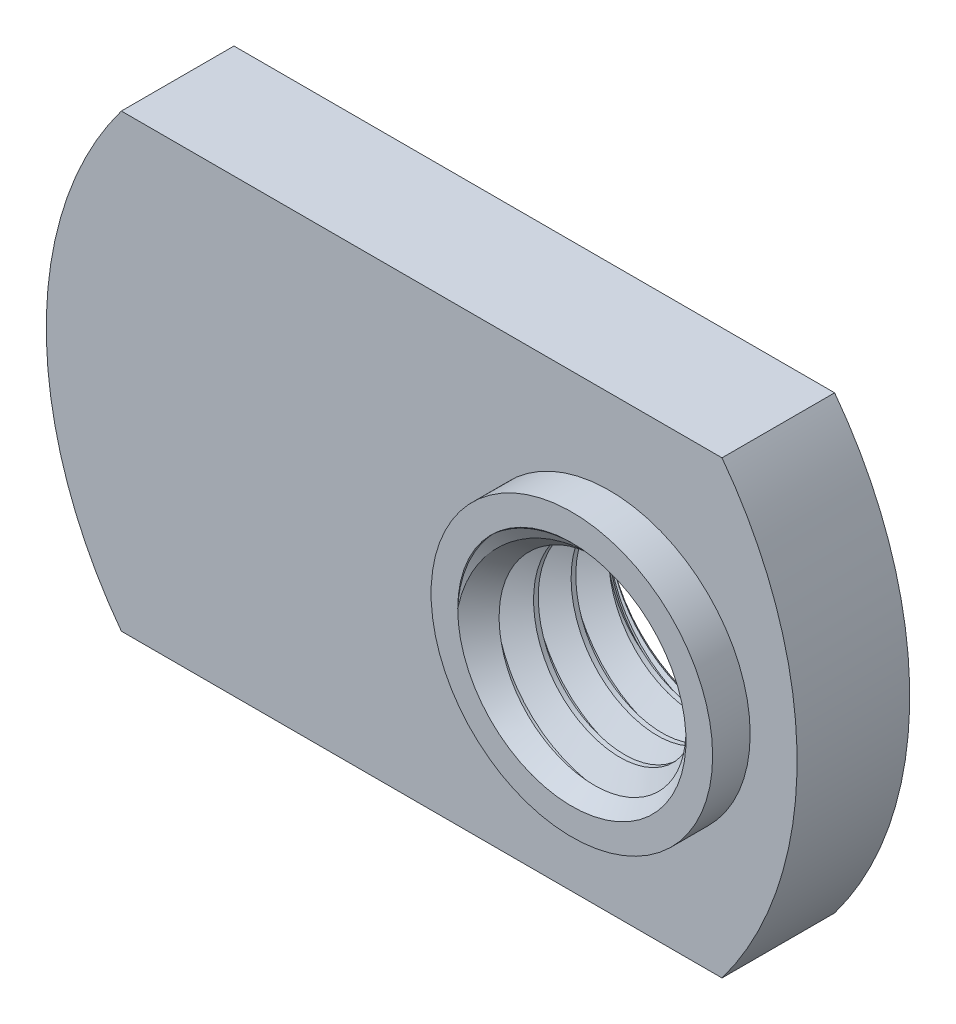
SolidWorks part; units mm, degrees
note: '?' marks a value the reader was unsure of.
ref_plane "Front Plane" through (0, 0, 0) normal (0, 0, 1) x (1, 0, 0)
ref_plane "Top Plane" through (0, 0, 0) normal (0, 1, 0) x (1, 0, 0)
ref_plane "Right Plane" through (0, 0, 0) normal (1, 0, 0) x (0, 0, -1)
sketch "Sketch1" plane through (0, 0, 0) normal (0, 0, 1) x (1, 0, 0)
  line L0 (-6.35, 4.7625) -> (6.35, 4.7625)
  line L1 (-6.35, -4.7625) -> (6.35, -4.7625)
  line L2 (0, 0) -> (3.9688, 0) construction
  line L3 (3.9688, 0) -> (7.9375, 0) construction
  arc A0 (6.35, -4.7625) -> (6.35, 4.7625) centre (0, 0) ccw
  arc A2 (-6.35, 4.7625) -> (-6.35, -4.7625) centre (0, 0) ccw
  circle A3 centre (3.9688, 0) radius 2.413
  dimension "D1" = 4.826
  dimension "width" = 9.525
extrude "Extrude1" add sketch "Sketch1" along normal blind 2.3813
sketch "Sketch2" plane through (0, 0, 2.3813) normal (0, 0, 1) x (1, 0, 0)
  circle A0 centre (3.9688, 0) radius 2.9766
  circle A1 centre (3.9688, 0) radius 2.413
  circle A2 centre (3.9688, 0) radius 2.413 construction
extrude "Extrude2" add sketch "Sketch2" along normal blind 0.7937
sketch "Sketch3" plane through (0, 0, 0) normal (0, 0, -1) x (-1, 0, 0)
  circle A1 centre (-3.9688, 0) radius 2.413
  circle A2 centre (-3.9688, 0) radius 2.413 construction
curve "Helix/Spiral1" pitch 0.7937 height 7.1437 turns 9 parameters "pitch"=0.7937
sketch "Sketch4" plane through (0, 0, 0) normal (0, 1, 0) x (1, 0, 0)
  line L0 (1.5557, 0.6945) -> (1.5557, 0)
  line L1 (1.5557, 0) -> (2.0713, 0.2977)
  line L2 (2.0713, 0.2977) -> (2.0713, 0.3969)
  line L3 (2.0713, 0.3969) -> (1.5557, 0.6945)
  line L4 (2.0713, 0.3473) -> (1.5557, 0.3473) construction
  line L5 (1.8135, 0.1488) -> (1.8135, 0.5457) construction
  dimension "D1" = 0.0992
  dimension "D2" = 0.3969
  dimension "D3" = 60
sweep "Sweep1" add profiles "Sketch4" path "Helix/Spiral1"
sketch "Sketch5" plane through (0, 0, 0) normal (0, 0, -1) x (-1, 0, 0)
  line L2 (-6.35, -4.7625) -> (6.35, -4.7625)
  line L3 (-6.35, -4.7625) -> (6.35, -4.7625)
  line L4 (6.35, 4.7625) -> (-6.35, 4.7625)
  line L5 (6.35, 4.7625) -> (-6.35, 4.7625)
  arc A1 (-6.35, 4.7625) -> (-6.35, -4.7625) centre (0, 0) ccw
  arc A2 (-6.35, 4.7625) -> (-6.35, -4.7625) centre (0, 0) ccw
  arc A4 (6.35, -4.7625) -> (6.35, 4.7625) centre (0, 0) ccw
  arc A5 (6.35, -4.7625) -> (6.35, 4.7625) centre (0, 0) ccw
  dimension "D1" = 0
extrude "Cut-Extrude1" cut sketch "Sketch5" along normal through all
sketch "Sketch6" plane through (0, 0, 0) normal (0, 0, -1) x (-1, 0, 0)
  circle A1 centre (-3.9688, 0) radius 2.413
  circle A2 centre (-3.9688, 0) radius 2.413 construction
extrude "Cut-Extrude2" cut sketch "Sketch6" against normal through all draft 45
sketch "Sketch7" plane through (0, 0, 3.175) normal (0, 0, 1) x (1, 0, 0)
  circle A1 centre (3.9688, 0) radius 2.9766
  circle A2 centre (3.9688, 0) radius 2.9766
  dimension "D1" = 0
extrude "Cut-Extrude3" cut sketch "Sketch7" along normal through all
sketch "Sketch8" plane through (0, 0, 3.175) normal (0, 0, 1) x (1, 0, 0)
  circle A1 centre (3.9688, 0) radius 2.413
  circle A2 centre (3.9688, 0) radius 2.413 construction
extrude "Cut-Extrude4" cut sketch "Sketch8" against normal through all draft 45
ref_axis "Center Axis 1" through (3.9688, 0, 0.5156) along (0, 0, 1)?
ref_plane "Contact Plane 1" through (0, 0, 2.3813) normal (0, 0, 1) x (1, 0, 0)
ref_plane "Contact Plane 2" through (0, 0, 0) normal (0, 0, -1) x (-1, 0, 0)
equation "\"D1@Sketch1\" = \"OD@Sketch2\""
equation "\"D3@Helix/Spiral1\" = \"height@Extrude2\"+.250"
equation "\"D1@Sketch4\" = \"pitch@Helix/Spiral1\"*.125"
equation "\"D2@Sketch4\" = \"pitch@Helix/Spiral1\"*.5"
